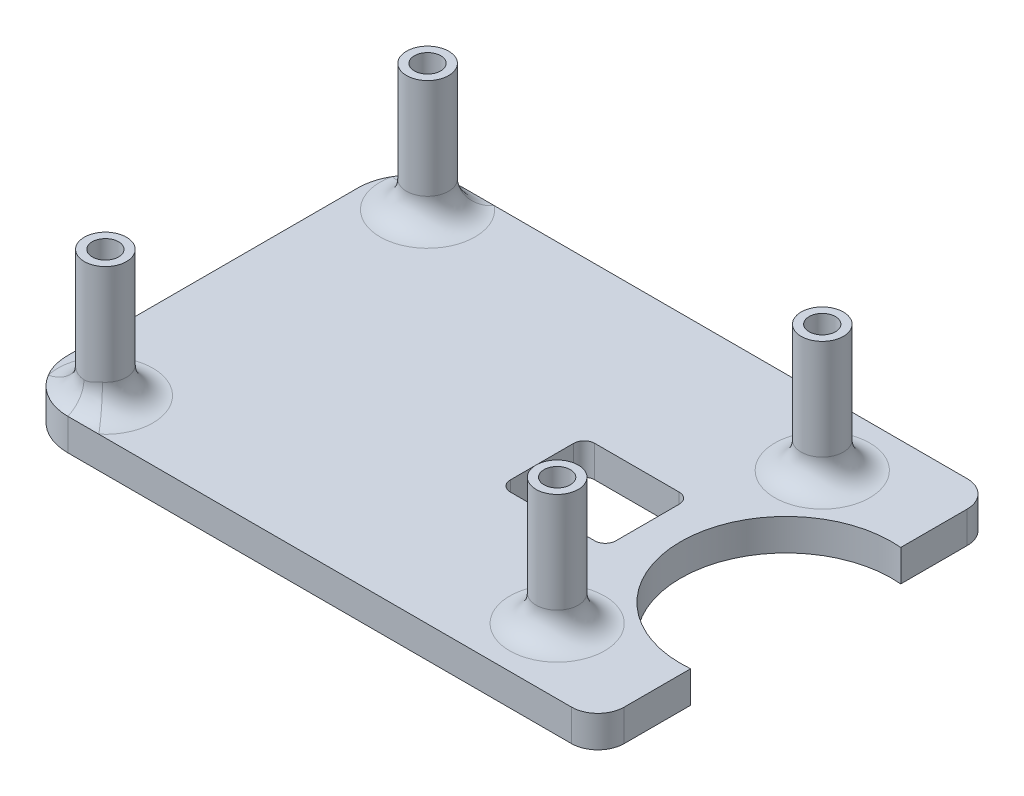
SolidWorks part; units mm, degrees
ref_plane "Plano frontal" through (0, 0, 0) normal (0, 0, 1) x (1, 0, 0)
ref_plane "Plano superior" through (0, 0, 0) normal (0, 1, 0) x (1, 0, 0)
ref_plane "Plano direito" through (0, 0, 0) normal (1, 0, 0) x (0, 0, -1)
sketch "Esboço1" plane through (0, 0, 0) normal (0, 1, 0) x (1, 0, 0)
  line L0 (0, 0) -> (-107.25, 0) construction
  line L1 (-96.6642, 30.535) -> (-96.6642, -30.535) construction
  line L2 (-73.2328, -37.99) -> (-73.2328, 37.99) construction
  line L3 (-16.4442, -25.125) -> (-16.4442, 25.125) construction
  circle A0 centre (-96.6642, 30.535) radius 4
  circle A1 centre (-96.6642, -30.535) radius 4
  circle A2 centre (-16.4442, 25.125) radius 4
  circle A3 centre (-16.4442, -25.125) radius 4
  point P9 (-96.6642, 0)
  point P10 (-16.4442, 0)
  point P18 (-73.2328, 0)
  dimension "D5" = 8
  dimension "D7" = 30.0279
  dimension "D1" = 75.98
  dimension "D2" = 107.25
  dimension "D3" = 50.25
  dimension "D4" = 61.07
  dimension "D6" = 80.22
extrude "Ressalto-extrusão1" add sketch "Esboço1" along normal blind 24
sketch "Esboço2" plane through (0, 0, 0) normal (0, -1, 0) x (1, 0, 0)
  line L0 (-107.25, 0) -> (-18.1735, 0) construction
  line L1 (3.6426, 19.9174) -> (3.6426, 32.5)
  line L2 (-16.4442, -25.125) -> (-16.4442, 25.125) construction
  line L3 (-96.8191, -37.5) -> (-1.3574, -37.5)
  line L4 (-106.8191, -27.5) -> (-106.8191, 27.5)
  line L5 (-96.8191, 37.5) -> (-1.3574, 37.5)
  line L6 (3.6426, -32.5) -> (3.6426, -19.9174)
  line L7 (-106.8191, -37.5) -> (3.6426, 37.5) construction
  line L8 (-106.8191, 37.5) -> (3.6426, -37.5) construction
  arc A0 (3.6426, 19.9174) -> (3.6426, -19.9174) centre (1.8265, 0) ccw
  arc A1 (-96.8191, -37.5) -> (-106.8191, -27.5) centre (-96.8191, -27.5) cw
  arc A2 (-106.8191, 27.5) -> (-96.8191, 37.5) centre (-96.8191, 27.5) cw
  arc A3 (-1.3574, -37.5) -> (3.6426, -32.5) centre (-1.3574, -32.5) ccw
  arc A4 (-1.3574, 37.5) -> (3.6426, 32.5) centre (-1.3574, 32.5) cw
  point P4 (-51.5882, 0)
  dimension "D1" = 10
  dimension "D2" = 5
  dimension "D3" = 20
  dimension "D4" = 55
extrude "Ressalto-extrusão2" add sketch "Esboço2" along normal blind 6
fillet "Filete1" radius 5 4 edges at (-96.6642, 0, -34.535) (-16.4442, 0, -29.125) (-16.4442, 0, 21.125) (-96.6642, 0, 34.535)
sketch "Esboço3" plane through (0, 24, 0) normal (0, 1, 0) x (1, 0, 0)
  line L0 (0, 0) -> (-107.25, 0) construction
  line L1 (-44.4442, 8) -> (-24.4442, 8)
  line L2 (-44.4442, 8) -> (-44.4442, -8)
  line L3 (-44.4442, -8) -> (-24.4442, -8)
  line L4 (-24.4442, 8) -> (-24.4442, -8)
  line L5 (-44.4442, 8) -> (-24.4442, -8) construction
  line L6 (-44.4442, -8) -> (-24.4442, 8) construction
  circle A0 centre (-96.6642, -30.535) radius 4 construction
  circle A1 centre (-16.4442, -25.125) radius 4 construction
  circle A2 centre (-16.4442, 25.125) radius 4 construction
  circle A3 centre (-96.6642, 30.535) radius 4 construction
  circle A4 centre (-96.6642, -30.535) radius 4
  circle A5 centre (-16.4442, -25.125) radius 4
  circle A6 centre (-16.4442, 25.125) radius 4
  circle A7 centre (-96.6642, 30.535) radius 4
  circle A8 centre (-96.6642, 30.535) radius 2.5
  circle A9 centre (-16.4442, 25.125) radius 2.5
  circle A10 centre (-16.4442, -25.125) radius 2.5
  circle A11 centre (-96.6642, -30.535) radius 2.5
  point P16 (-34.4442, 0)
  dimension "D1" = 5
  dimension "D2" = 5
  dimension "D3" = 5
  dimension "D4" = 5
  dimension "D5" = 20
  dimension "D6" = 16
  dimension "D7" = 18
extrude "Corte-extrusão1" cut sketch "Esboço3" against normal through all both and the other way through all contours A8 | A9 | A10 | A11 | L2 L1 L4 L3
fillet "Filete2" radius 2 4 edges at (-44.4442, -3, 8) (-24.4442, -3, 8) (-24.4442, -3, -8) (-44.4442, -3, -8)
